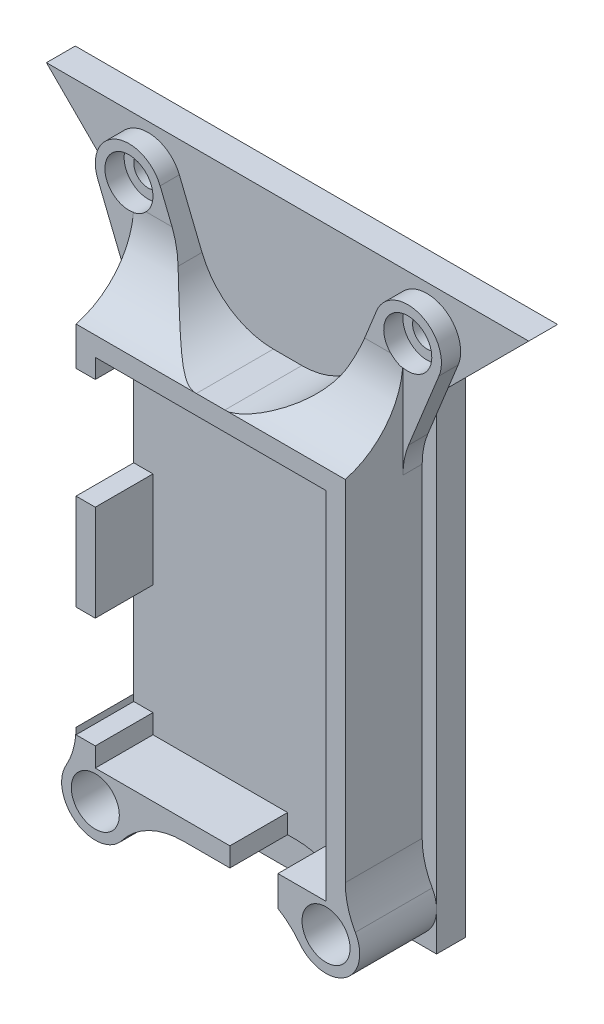
SolidWorks part; units mm, degrees
other "PlateRear"
ref_plane "Front Plane" through (0, 0, 0) normal (0, 0, 1) x (1, 0, 0)
ref_plane "Top Plane" through (0, 0, 0) normal (0, 1, 0) x (1, 0, 0)
ref_plane "Right Plane" through (0, 0, 0) normal (1, 0, 0) x (0, 0, -1)
sketch "Sketch1" plane through (0, 0, 0) normal (0, 0, 1) x (1, 0, 0)
  line L1 (0, 0) -> (31, 0)
  line L2 (0, 0) -> (0, 50.4189)
  line L3 (-9.5811, 60) -> (40.5811, 60)
  line L4 (31, 0) -> (31, 50.4189)
  line L5 (40.5811, 60) -> (31, 50.4189)
  line L7 (-9.5811, 60) -> (0, 50.4189)
  circle A0 centre (30, 55.5) radius 1.5
  circle A1 centre (27.5, 44) radius 1.5
  circle A4 centre (27.5, 4) radius 1.5
  circle A5 centre (3.5, 4) radius 1.5
  circle A7 centre (3.5, 44) radius 1.5
  circle A9 centre (1, 55.5) radius 1.5
  point P1 (0, 0)
  point P2 (31, 50.4189)
  point P13 (0, 0)
  point P14 (0, 0)
  point P15 (0, 0)
  point P16 (0, 0)
  point P21 (0, 0)
  point P22 (-48.7808, 46.3753)
  point P25 (0, 0)
  point P26 (0, 0)
  point P29 (15.5, 60)
  point P30 (0, 0)
  point P31 (0, 0)
  point P32 (0, 0)
  point P34 (-1.6846, 60)
  point P35 (-1.5411, 60)
  point P36 (0, 0)
  point P37 (0, 0)
  point P38 (40.3628, 60)
  point P39 (40.5811, 60)
  point P40 (-62.9153, 53.7651)
  dimension "D4" = 3
  dimension "D5" = 21
  dimension "D6" = 2
  dimension "D7" = 2
  dimension "D8" = 21
  dimension "D9" = 2.5
  dimension "D10" = 37
  dimension "D11" = 2.8
  dimension "D12" = 29
  dimension "D13" = 14.5
  dimension "D14" = 11.5
  dimension "D15" = 3
  dimension "D1" = 45
  dimension "D2" = 45
  dimension "D3" = 31
extrude "Boss-Extrude1" add sketch "Sketch1" along normal blind 3
sketch "Sketch2" plane through (0, 0, 3) normal (0, 0, 1) x (1, 0, 0)
  line L0 (15.5, -2.1541) -> (15.5, -12.6171) construction
  line L1 (14.015, 46) -> (16.985, 46)
  line L4 (29.5, 43.3836) -> (29.5, 9.6789)
  line L5 (18.3759, 5) -> (12.6241, 5)
  line L6 (0, 0) -> (31, 0) construction
  line L7 (33.244, 54.1861) -> (30.0851, 46.3869)
  line L8 (26.756, 56.8139) -> (24.3999, 50.9968)
  line L9 (4.244, 56.8139) -> (6.6001, 50.9968)
  line L10 (-2.244, 54.1861) -> (0.9149, 46.3869)
  line L11 (1.5, 43.3836) -> (1.5, 9.6789)
  circle A0 centre (27.5, 44) radius 1.5 construction
  circle A1 centre (30, 55.5) radius 1.5 construction
  circle A3 centre (27.5, 4) radius 1.5 construction
  circle A4 centre (27.5, 4) radius 1.5 construction
  circle A5 centre (27.5, 4) radius 2.5
  circle A7 centre (30, 55.5) radius 2.5
  arc A8 (33.244, 54.1861) -> (26.756, 56.8139) centre (30, 55.5) ccw
  arc A9 (24.7231, 1.8696) -> (30.5435, 5.7284) centre (27.5, 4) ccw
  arc A10 (29.5, 43.3836) -> (30.0851, 46.3869) centre (37.5, 43.3836) cw
  arc A11 (16.985, 46) -> (24.3999, 50.9968) centre (16.985, 54) ccw
  arc A12 (24.7231, 1.8696) -> (18.3759, 5) centre (18.3759, -3) ccw
  arc A13 (30.5435, 5.7284) -> (29.5, 9.6789) centre (37.5, 9.6789) cw
  circle A14 centre (3.5, 4) radius 1.5 construction
  arc A15 (0.4565, 5.7284) -> (1.5, 9.6789) centre (-6.5, 9.6789) ccw
  arc A16 (6.2769, 1.8696) -> (12.6241, 5) centre (12.6241, -3) cw
  arc A17 (14.015, 46) -> (6.6001, 50.9968) centre (14.015, 54) cw
  arc A18 (1.5, 43.3836) -> (0.9149, 46.3869) centre (-6.5, 43.3836) ccw
  arc A19 (6.2769, 1.8696) -> (0.4565, 5.7284) centre (3.5, 4) cw
  arc A20 (-2.244, 54.1861) -> (4.244, 56.8139) centre (1, 55.5) cw
  circle A21 centre (1, 55.5) radius 2.5
  circle A22 centre (3.5, 4) radius 2.5
  point P6 (15.5, 0)
  point P7 (15.5, 46)
  point P23 (0, 0)
  point P53 (15.5, 5)
  point P54 (0, 0)
  dimension "D4" = 7
  dimension "D5" = 5
  dimension "D6" = 7
  dimension "D7" = 5
  dimension "D3" = 8
  dimension "D1" = 41
  dimension "D2" = 2
  dimension "D8" = 14
extrude "Boss-Extrude2" add sketch "Sketch2" along normal blind 2 separate body
sketch "Sketch3" plane through (0, 0, 5) normal (0, 0, 1) x (1, 0, 0)
  line L0 (16.985, 46) -> (14.015, 46) construction
  line L1 (3.5, 44) -> (27.5, 44)
  line L2 (3.5, 44) -> (3.5, 42)
  line L3 (3.5, 7) -> (17.5, 7)
  line L4 (27.5, 44) -> (27.5, 7)
  line L5 (29.5, 9.6789) -> (29.5, 43.3836) construction
  line L6 (1.5, 43.3836) -> (1.5, 9.6789) construction
  line L7 (12.6241, 5) -> (18.3759, 5) construction
  line L8 (3.5, 42) -> (1.5, 42)
  line L13 (1.5, 42) -> (1.5, 46)
  line L14 (1.5, 46) -> (29.5, 46)
  line L15 (29.5, 46) -> (29.5, 9.6789)
  line L16 (17.5, 5) -> (12.6241, 5)
  line L17 (1.5, 9.6789) -> (1.5, 9)
  line L18 (1.5, 9) -> (3.5, 9)
  line L19 (3.5, 20.5) -> (1.5, 20.5)
  line L20 (1.5, 20.5) -> (1.5, 30.5)
  line L21 (1.5, 30.5) -> (3.5, 30.5)
  line L22 (3.5, 9) -> (3.5, 7)
  line L23 (3.5, 20.5) -> (3.5, 30.5)
  line L26 (17.5, 7) -> (17.5, 5)
  line L28 (22.5, 7) -> (22.5, 3.855)
  line L30 (22.5, 7) -> (27.5, 7)
  arc A1 (29.5, 9.6789) -> (30.5435, 5.7284) centre (37.5, 9.6789) ccw construction
  circle A2 centre (27.5, 4) radius 2.5 construction
  circle A3 centre (27.5, 4) radius 2.5
  arc A4 (24.7231, 1.8696) -> (30.5435, 5.7284) centre (27.5, 4) ccw
  circle A5 centre (3.5, 4) radius 2.5 construction
  circle A6 centre (3.5, 4) radius 2.5
  arc A7 (24.7231, 1.8696) -> (30.5435, 5.7284) centre (27.5, 4) ccw construction
  arc A8 (0.4565, 5.7284) -> (6.2769, 1.8696) centre (3.5, 4) ccw
  arc A9 (0.4565, 5.7284) -> (6.2769, 1.8696) centre (3.5, 4) ccw construction
  arc A10 (24.7231, 1.8696) -> (18.3759, 5) centre (18.3759, -3) ccw construction
  arc A11 (12.6241, 5) -> (6.2769, 1.8696) centre (12.6241, -3) ccw construction
  arc A12 (0.4565, 5.7284) -> (1.5, 9.6789) centre (-6.5, 9.6789) ccw construction
  arc A13 (29.5, 9.6789) -> (30.5435, 5.7284) centre (37.5, 9.6789) ccw
  arc A14 (24.7231, 1.8696) -> (22.5, 3.855) centre (18.3759, -3) ccw
  arc A15 (12.6241, 5) -> (6.2769, 1.8696) centre (12.6241, -3) ccw
  arc A16 (0.4565, 5.7284) -> (1.5, 9.6789) centre (-6.5, 9.6789) ccw
  point P50 (0, 0)
  point P51 (1.5, 25.5)
  point P52 (0, 0)
  point P53 (0, 0)
  point P54 (27.5, 25.5)
  dimension "D1" = 2
  dimension "D2" = 2
  dimension "D3" = 2
  dimension "D4" = 2
  dimension "D5" = 5
  dimension "D6" = 14
  dimension "D7" = 4
  dimension "D8" = 10
  dimension "D9" = 2
extrude "Boss-Extrude3" add sketch "Sketch3" along normal blind 6
fillet "Fillet1" radius 8 2 edges at (7.7575, 46, 5) (23.2425, 46, 5)
